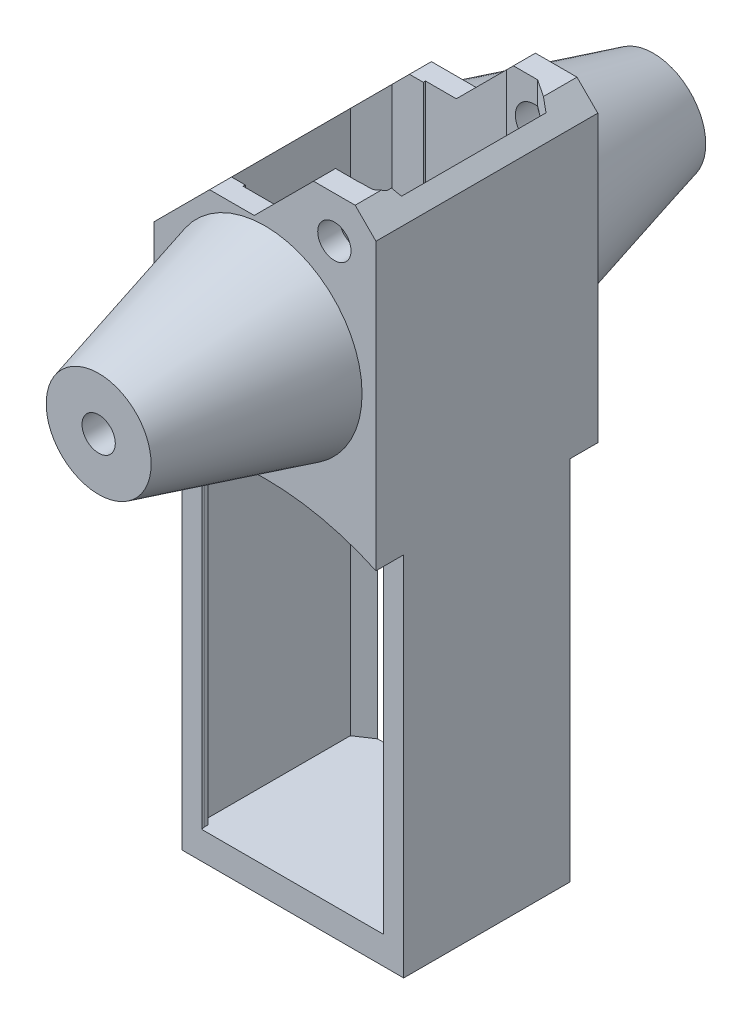
SolidWorks part; units mm, degrees
ref_plane "Front Plane" through (0, 0, 0) normal (0, 0, 1) x (1, 0, 0)
ref_plane "Top Plane" through (0, 0, 0) normal (0, 1, 0) x (1, 0, 0)
ref_plane "Right Plane" through (0, 0, 0) normal (1, 0, 0) x (0, 0, -1)
sketch "Sketch1" plane through (0, 0, 0) normal (0, 1, 0) x (1, 0, 0)
  line L0 (4.7625, -10.1854) -> (8.3298, -10.1854)
  line L5 (-4.7625, 10.1854) -> (-4.7625, 10.4394)
  line L6 (-12.7, -12.7) -> (12.7, -12.7)
  line L7 (4.7625, 10.1854) -> (8.3298, 10.1854)
  line L8 (-8.3298, 10.1854) -> (-11.2014, 8.271)
  line L9 (-8, 10.1) -> (-11, 8.1) construction
  line L10 (0, 0) -> (-11.2014, 0) construction
  line L11 (0, 0) -> (0, 10.4394) construction
  line L12 (-8.3298, -10.1854) -> (-8.3769, -10.154)
  line L13 (8.3298, -10.1854) -> (8.3769, -10.154)
  line L14 (8.3298, 10.1854) -> (11.2014, 8.271)
  line L15 (-8.3298, 10.1854) -> (-4.7625, 10.1854)
  line L16 (-12.7, 12.7) -> (-12.7, -12.7)
  line L17 (12.7, 12.7) -> (12.7, -12.7)
  line L34 (-10.504, -8.7359) -> (-11.2014, -8.271)
  line L35 (8.3769, -10.154) -> (9.4165, -10.154)
  line L36 (9.5863, -10.1409) -> (9.6154, -10.1409)
  line L37 (-9.5863, -10.1409) -> (-9.6154, -10.1409)
  line L38 (-8.75, -10.154) -> (-9.4165, -10.154)
  line L39 (-10.504, -9.1) -> (-10.504, -8.9)
  line L40 (-9.5863, -10.1409) -> (-9.6154, -10.1409)
  line L41 (-8.3769, -10.154) -> (-9.4165, -10.154)
  line L42 (-10.504, -9.1) -> (-10.504, -8.7359)
  line L43 (10.504, -9.1) -> (10.504, -8.7359)
  line L44 (10.504, -8.7359) -> (11.2014, -8.271)
  line L284 (-12.7, 12.7) -> (12.7, 12.7)
  line L286 (-12.7, -12.7) -> (12.7, 12.7) construction
  line L287 (-12.7, 12.7) -> (12.7, -12.7) construction
  line L288 (-8.3298, -10.1854) -> (-4.7625, -10.1854)
  line L289 (-11.2014, -8.271) -> (-11.2014, 8.271)
  line L291 (11.2014, -8.271) -> (11.2014, 8.271)
  line L326 (-4.7625, 10.4394) -> (4.7625, 10.4394)
  line L327 (4.7625, 10.4394) -> (4.7625, 10.1854)
  line L328 (-4.7625, -10.1854) -> (-4.7625, -10.4394)
  line L335 (-4.7625, -10.4394) -> (4.7625, -10.4394)
  line L338 (4.7625, -10.4394) -> (4.7625, -10.1854)
  arc A7 (9.5863, -10.1409) -> (9.4165, -10.154) centre (9.4168, -9.0458) cw
  arc A8 (-9.5863, -10.1409) -> (-9.4165, -10.154) centre (-9.4168, -9.0458) ccw
  arc A9 (-10.504, -9.1) -> (-9.6154, -10.1409) centre (-9.45, -9.1) ccw
  arc A10 (-9.5863, -10.1409) -> (-9.4165, -10.154) centre (-9.4168, -9.0458) ccw
  arc A11 (-10.504, -9.1) -> (-9.6154, -10.1409) centre (-9.45, -9.1) ccw
  arc A12 (10.504, -9.1) -> (9.6154, -10.1409) centre (9.45, -9.1) cw
  point P0 (0, 0)
  point P6 (0, 0)
  point P15 (0, 10.4394)
  point P23 (0, -10.4394)
  dimension "D1" = 25.4
  dimension "D2" = 25.4
  dimension "D3" = 0.254
  dimension "D5" = 9.525
  dimension "D6" = 22.4028
  dimension "D7" = 0.254
  dimension "D8" = 20.3708
  dimension "D9" = 0.254
  dimension "D15" = 0.254
extrude "Boss-Extrude1" add sketch "Sketch1" along normal blind 67.056
sketch "Sketch4" plane through (0, 0, 0) normal (0, -1, 0) x (-1, 0, 0)
  line L1 (12.7, -12.7) -> (-12.7, -12.7)
  line L2 (12.7, -12.7) -> (12.7, 12.7)
  line L3 (12.7, 12.7) -> (-12.7, 12.7)
  line L4 (-12.7, -12.7) -> (-12.7, 12.7)
extrude "Boss-Extrude4" add sketch "Sketch4" along normal blind 3.175
sketch "Sketch5" plane through (0, 0, -12.7) normal (0, 0, -1) x (-1, 0, 0)
  circle A0 centre (0, 11.43) radius 30.1625
  dimension "D2" = 60.325
  dimension "D1" = 11.43
extrude "Cut-Extrude1" cut sketch "Sketch5" against normal blind 3.175
mirror "Mirror1" about plane through (0, 0, 0) normal (0, 0, 1) of "Cut-Extrude1"
sketch "Sketch7" plane through (0, 0, 12.7) normal (0, 0, 1) x (1, 0, 0)
  circle A0 centre (0, 55.5371) radius 11.1125
  circle A1 centre (0, 11.0871) radius 4.7625 construction
  dimension "D2" = 22.225
  dimension "D1" = 44.45
extrude "Boss-Extrude6" add sketch "Sketch7" along normal blind 19.05 draft 15
sketch "Sketch8" plane through (0, 0, 31.75) normal (0, 0, 1) x (1, 0, 0)
  circle A0 centre (0, 55.5371) radius 1.905
  dimension "D1" = 3.81
extrude "Cut-Extrude2" cut sketch "Sketch8" against normal blind 12.7
mirror "Mirror3" about plane through (0, 0, 0) normal (0, 0, 1) of "Cut-Extrude2", "Boss-Extrude6"
sketch "Sketch12" plane through (0, 0, -12.7) normal (0, 0, -1) x (-1, 0, 0)
  line L0 (-12.7, 67.056) -> (-12.7, 71.4692)
  line L1 (-12.7, 71.4692) -> (-10.3187, 73.8505)
  line L2 (-10.3187, 73.8505) -> (-5.5562, 73.8505)
  line L3 (-5.5562, 73.8505) -> (1.2383, 67.056)
  line L4 (-12.7, 67.056) -> (12.7, 67.056) construction
  line L5 (-12.7, 67.056) -> (1.2383, 67.056)
  circle A0 centre (-7.9375, 69.088) radius 1.905
  point P10 (-7.9375, 73.8505)
  dimension "D1" = 3.81
  dimension "D2" = 45
  dimension "D3" = 4.7625
  dimension "D4" = 4.7625
  dimension "D5" = 4.7625
  dimension "D6" = 2.032
extrude "Boss-Extrude8" add sketch "Sketch12" against normal up to surface (25.4 mm away) up to face at (11.1125, 55.5371, 12.7)
sketch "Sketch13" plane through (0, 67.056, 0) normal (0, -1, 0) x (1, 0, 0)
  line L14 (4.7625, 10.1854) -> (4.7625, 10.4394)
  line L15 (4.7625, 10.4394) -> (-1.2383, 10.4394)
  line L16 (-1.2383, 10.4394) -> (-1.2383, -10.4394)
  line L17 (-1.2383, -10.4394) -> (4.7625, -10.4394)
  line L18 (4.7625, -10.4394) -> (4.7625, -10.1854)
  line L19 (4.7625, -10.1854) -> (8.3298, -10.1854)
  line L20 (8.3298, -10.1854) -> (11.2014, -8.271)
  line L21 (11.2014, -8.271) -> (11.2014, 8.271)
  line L22 (11.2014, 8.271) -> (10.504, 8.7359)
  line L23 (10.504, 8.7359) -> (10.504, 9.1)
  line L24 (9.6154, 10.1409) -> (9.5863, 10.1409)
  line L25 (9.4165, 10.154) -> (8.3769, 10.154)
  line L26 (8.3769, 10.154) -> (8.3298, 10.1854)
  line L27 (8.3298, 10.1854) -> (4.7625, 10.1854)
  line L28 (4.7625, 10.1854) -> (4.7625, 10.4394)
  line L29 (4.7625, 10.4394) -> (-1.2383, 10.4394)
  line L30 (-1.2383, 10.4394) -> (-1.2383, -10.4394)
  line L31 (-1.2383, -10.4394) -> (4.7625, -10.4394)
  line L32 (4.7625, -10.4394) -> (4.7625, -10.1854)
  line L33 (4.7625, -10.1854) -> (8.3298, -10.1854)
  line L34 (8.3298, -10.1854) -> (11.2014, -8.271)
  line L35 (11.2014, -8.271) -> (11.2014, 8.271)
  line L36 (11.2014, 8.271) -> (10.504, 8.7359)
  line L37 (10.504, 8.7359) -> (10.504, 9.1)
  line L38 (9.6154, 10.1409) -> (9.5863, 10.1409)
  line L39 (9.4165, 10.154) -> (8.3769, 10.154)
  line L40 (8.3769, 10.154) -> (8.3298, 10.1854)
  line L41 (8.3298, 10.1854) -> (4.7625, 10.1854)
  arc A2 (10.504, 9.1) -> (9.6154, 10.1409) centre (9.45, 9.1) ccw
  arc A3 (9.5863, 10.1409) -> (9.4165, 10.154) centre (9.4168, 9.0458) ccw
  arc A4 (10.504, 9.1) -> (9.6154, 10.1409) centre (9.45, 9.1) ccw
  arc A5 (9.5863, 10.1409) -> (9.4165, 10.154) centre (9.4168, 9.0458) ccw
  dimension "D1" = 0
extrude "Cut-Extrude5" cut sketch "Sketch13" against normal up to next
sketch "Sketch14" plane through (0, 0, -12.7) normal (0, 0, -1) x (-1, 0, 0)
  circle A0 centre (-7.9375, 69.088) radius 2.159
  dimension "D1" = 4.318
extrude "Cut-Extrude6" cut sketch "Sketch14" against normal up to next
chamfer "Chamfer3" distance 6.35 angle 45 1 edges at (-12.7, 67.056, 0)
